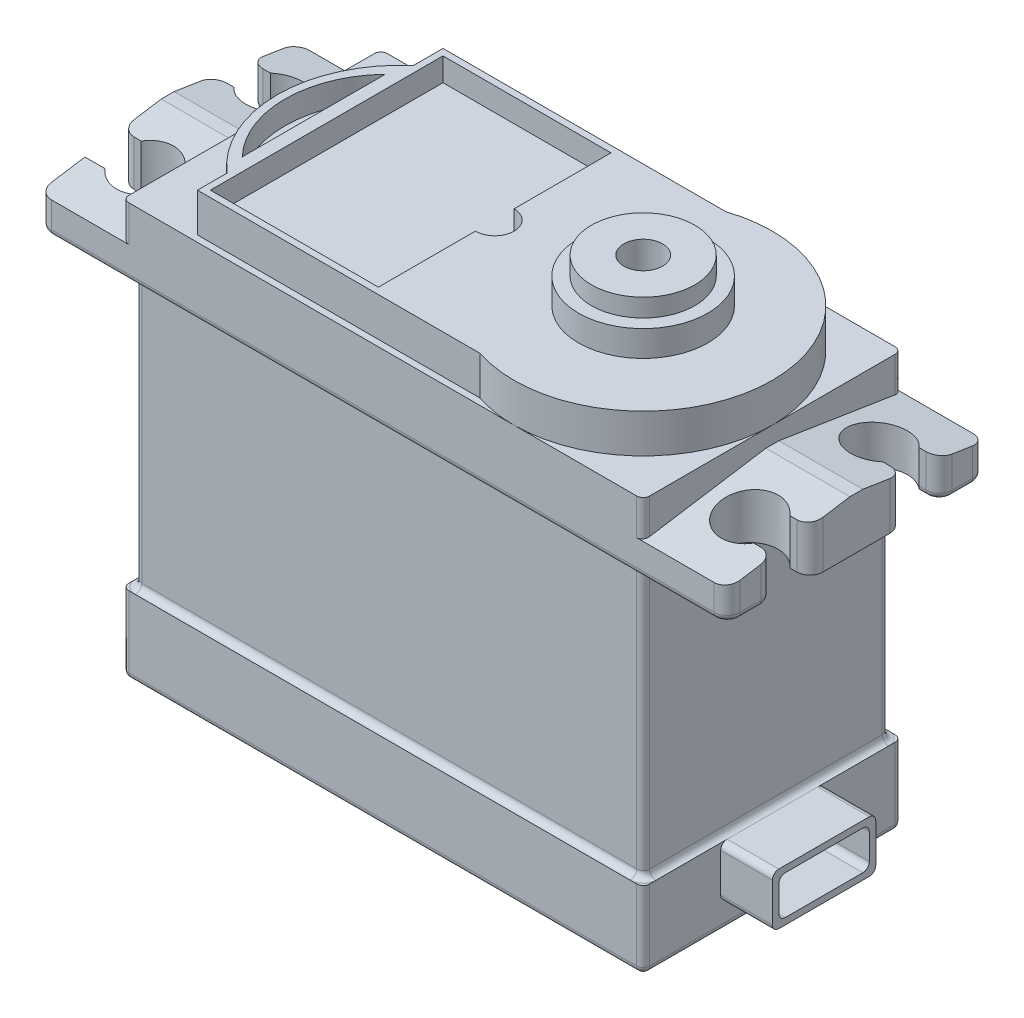
SolidWorks part; units mm, degrees
ref_plane "前基準面" through (0, 0, 0) normal (0, 0, 1) x (1, 0, 0)
ref_plane "上基準面" through (0, 0, 0) normal (0, 1, 0) x (1, 0, 0)
ref_plane "右基準面" through (0, 0, 0) normal (1, 0, 0) x (0, 0, -1)
sketch "草圖2" plane through (0, 0, 0) normal (0, 0, 1) x (1, 0, 0)
  line L1 (-17.6643, 8.7825) -> (22.6357, 8.7825)
  line L2 (-17.6643, 8.7825) -> (-17.6643, -23.2175)
  line L3 (-17.6643, -23.2175) -> (22.6357, -23.2175)
  line L4 (22.6357, 8.7825) -> (22.6357, -23.2175)
  dimension "D1" = 40.3
  dimension "D2" = 32
extrude "填料-伸長1" add sketch "草圖2" along normal blind 20 contours L2 L1 L4 L3
sketch "草圖3" plane through (22.6357, 0, 0) normal (1, 0, 0) x (0, 0, -1)
  line L2 (-20, 8.7825) -> (-20, -23.2175) construction
  line L3 (-20, 7.4825) -> (0, 7.4825)
  line L4 (-20, 7.4825) -> (-20, 3.4825)
  line L5 (-20, 3.4825) -> (0, 3.4825)
  line L6 (0, 7.4825) -> (0, 3.4825)
  line L7 (0, 8.7825) -> (0, -23.2175) construction
  line L9 (-20, -23.2175) -> (0, -23.2175) construction
  point P14 (0, 0)
  dimension "D1" = 26.7
  dimension "D2" = 4
extrude "填料-伸長2" add sketch "草圖3" along normal blind 6.5
sketch "草圖13" plane through (29.1357, 0, 0) normal (1, 0, 0) x (0, 0, -1)
  line L0 (-10, 7.4825) -> (-10, 3.4825) construction
  line L1 (0, 7.4825) -> (-20, 7.4825) construction
  line L2 (-20, 3.4825) -> (0, 3.4825) construction
  line L3 (-10.5, 7.4825) -> (-20, 5.9825)
  line L4 (-9.5, 3.4825) -> (-10.5, 3.4825)
  line L5 (-9.5, 3.4825) -> (-9.5, 7.4825)
  line L6 (-9.5, 7.4825) -> (-10.5, 7.4825)
  line L7 (-10.5, 3.4825) -> (-10.5, 7.4825)
  line L8 (-20, 7.4825) -> (-20, 3.4825) construction
  line L9 (-9.5, 7.4825) -> (0, 5.9825)
  line L10 (0, 3.4825) -> (0, 7.4825) construction
  point P10 (-10, 7.4825)
  line M5 (-20, 7.4825) -> (-20, 3.4825)
  line M7 (0, 3.4825) -> (0, 7.4825)
  line M8 (0, 7.4825) -> (-20, 7.4825)
  dimension "D1" = 1
  dimension "D2" = 2.5
  dimension "D3" = 2.5
extrude "除料-伸長4" cut sketch "草圖13" against normal up to surface (6.5 mm away) contours L3 M8 M5 | L9 M8 M7 region at (29.1357, 6.9825, 3.1667) region at (29.1357, 6.9825, 16.8333) up to face at (22.6357, 8.1325, 10)
sketch "草圖4" plane through (-17.6643, 0, 0) normal (-1, 0, 0) x (0, 0, 1)
  line L0 (10, -23.2175) -> (10, 3.3825) construction
  line L1 (20, -23.2175) -> (0, -23.2175) construction
  line L2 (0, 8.7825) -> (0, -23.2175) construction
  line L3 (0, 7.4825) -> (20, 7.4825)
  line L4 (0, 7.4825) -> (0, 3.4825)
  line L5 (0, 3.4825) -> (20, 3.4825)
  line L6 (20, 7.4825) -> (20, 3.4825)
  dimension "D1" = 26.6
  dimension "D2" = 4
extrude "填料-伸長3" add sketch "草圖4" along normal blind 6.5
sketch "草圖14" plane through (-24.1643, 0, 0) normal (-1, 0, 0) x (0, 0, 1)
  line L0 (10, 7.4825) -> (10, 3.4825) construction
  line L1 (20, 7.4825) -> (0, 7.4825) construction
  line L2 (0, 3.4825) -> (20, 3.4825) construction
  line L3 (9.5, 7.4825) -> (0, 5.9825)
  line L4 (9.5, 7.4825) -> (10.5, 7.4825)
  line L5 (9.5, 7.4825) -> (9.5, 3.4825)
  line L6 (9.5, 3.4825) -> (10.5, 3.4825)
  line L7 (10.5, 7.4825) -> (10.5, 3.4825)
  line L8 (0, 7.4825) -> (0, 3.4825) construction
  line L9 (10.5, 7.4825) -> (20, 5.9825)
  line L10 (20, 3.4825) -> (20, 7.4825) construction
  point P10 (10, 3.4825)
  line M5 (0, 7.4825) -> (0, 3.4825)
  line M7 (20, 3.4825) -> (20, 7.4825)
  line M8 (20, 7.4825) -> (0, 7.4825)
  dimension "D1" = 1
  dimension "D2" = 2.5
  dimension "D3" = 2.5
extrude "除料-伸長5" cut sketch "草圖14" against normal up to surface (6.5 mm away) contours L3 M8 M5 | L9 M8 M7 region at (-24.1643, 6.9825, 16.8333) region at (-24.1643, 6.9825, 3.1667) up to face at (-17.6643, 8.1325, 10)
sketch "草圖16" plane through (0, 0, 0) normal (0, 1, 0) x (1, 0, 0)
  line L0 (2.4857, 0) -> (2.4857, -20) construction
  line L1 (-24.1643, -20) -> (29.1357, -20)
  line L2 (-24.1643, -20) -> (-24.1643, 0)
  line L3 (-24.1643, 0) -> (29.1357, 0)
  line L4 (29.1357, -20) -> (29.1357, 0)
  line L5 (-17.6643, 0) -> (-24.1643, 0)
  line L6 (-20.9143, 0) -> (-20.9143, -20) construction
  line L7 (-24.1643, -10) -> (2.4857, -10) construction
  line L8 (-22.6114, -3.6) -> (-24.1643, -3.6)
  line L10 (-22.6114, -6.4) -> (-24.1643, -6.4)
  line L11 (-24.1643, -3.6) -> (-24.1643, -6.4)
  line L12 (-22.6114, -16.4) -> (-24.1643, -16.4)
  line L13 (-22.6114, -13.6) -> (-24.1643, -13.6)
  line L14 (27.5828, -16.4) -> (29.1357, -16.4)
  line L15 (27.5828, -13.6) -> (29.1357, -13.6)
  line L16 (27.5828, -3.6) -> (29.1357, -3.6)
  line L17 (27.5828, -6.4) -> (29.1357, -6.4)
  arc A0 (-22.6114, -6.4) -> (-22.6114, -3.6) centre (-20.9143, -5) ccw
  arc A1 (-22.6114, -13.6) -> (-22.6114, -16.4) centre (-20.9143, -15) cw
  arc A2 (27.5828, -13.6) -> (27.5828, -16.4) centre (25.8857, -15) ccw
  arc A3 (27.5828, -6.4) -> (27.5828, -3.6) centre (25.8857, -5) cw
  point P14 (-20.9143, -10)
  dimension "D1" = 4.4
  dimension "D2" = 5
  dimension "D3" = 3.6
  dimension "D4" = 3.1
extrude "除料-伸長6" cut sketch "草圖16" against normal blind 1.5 and the other way through all contours L10 A0 L8 L2 | A1 L13 L2 L12 | L15 A2 L14 L4 | A3 L17 L4 L16 region at (-21.3944, 0, 15) region at (26.3658, 0, 15) region at (-21.3944, 0, 5) region at (26.3658, 0, 5)
sketch "草圖7" plane through (22.6357, 0, 0) normal (1, 0, 0) x (0, 0, -1)
  line L1 (-20, -23.2175) -> (0, -23.2175) construction
  line L4 (-14, -17.2175) -> (-6, -17.2175)
  line L5 (-14, -17.2175) -> (-14, -21.2175)
  line L6 (-14, -21.2175) -> (-6, -21.2175)
  line L7 (-6, -17.2175) -> (-6, -21.2175)
  line L8 (-14, -17.2175) -> (-6, -21.2175) construction
  line L9 (-14, -21.2175) -> (-6, -17.2175) construction
  line L10 (-13.5, -17.7175) -> (-6.5, -17.7175)
  line L11 (-13.5, -17.7175) -> (-13.5, -20.7175)
  line L12 (-13.5, -20.7175) -> (-6.5, -20.7175)
  line L13 (-6.5, -17.7175) -> (-6.5, -20.7175)
  line L14 (-13.5, -17.7175) -> (-6.5, -20.7175) construction
  line L15 (-13.5, -20.7175) -> (-6.5, -17.7175) construction
  point P6 (-10, -19.2175)
  point P11 (-10, -19.2175)
  point P16 (0, 0)
  dimension "D1" = 2
  dimension "D2" = 8
  dimension "D3" = 4
  dimension "D4" = 0.5
  dimension "D5" = 0.5
extrude "填料-伸長4" add sketch "草圖7" along normal blind 4
sketch "草圖8" plane through (0, 8.7825, 0) normal (0, 1, 0) x (1, 0, 0)
  line L0 (-12.3544, -17.2064) -> (-12.3544, -19.5)
  line L1 (9.5132, -0.5) -> (-12.3544, -0.5)
  line L3 (-17.6643, -20) -> (-17.6643, 0) construction
  line L4 (9.5132, -19.5) -> (-12.3544, -19.5)
  line L5 (-12.3544, -0.5) -> (-12.3544, -2.7936)
  arc A0 (9.5132, -19.5) -> (9.5132, -0.5) centre (12.6357, -10) ccw
  arc A1 (-12.3544, -2.7936) -> (-12.3544, -17.2064) centre (-6.1643, -10) ccw
  point P0 (-15.6643, -10)
  point P10 (22.6357, -10)
  dimension "D2" = 9.5
  dimension "D1" = 10
  dimension "D3" = 2
extrude "填料-伸長5" add sketch "草圖8" along normal blind 3
sketch "草圖9" plane through (0, 11.7825, 0) normal (0, 1, 0) x (1, 0, 0)
  line L0 (22.6357, -10) -> (-15.6643, -10) construction
  arc A0 (9.5132, -19.5) -> (9.5132, -0.5) centre (12.6357, -10) ccw construction
  arc A1 (-12.3544, -2.7936) -> (-12.3544, -17.2064) centre (-6.1643, -10) ccw construction
  circle A2 centre (12.6357, -10) radius 5
  dimension "D1" = 10
extrude "填料-伸長6" add sketch "草圖9" along normal blind 2
sketch "草圖10" plane through (0, 13.7825, 0) normal (0, 1, 0) x (1, 0, 0)
  circle A0 centre (12.6357, -10) radius 4
  circle A1 centre (12.6357, -10) radius 5 construction
  dimension "D1" = 1
extrude "填料-伸長7" add sketch "草圖10" along normal blind 1.4
sketch "草圖11" plane through (0, 15.1825, 0) normal (0, 1, 0) x (1, 0, 0)
  circle A0 centre (12.6357, -10) radius 1.5
  dimension "D1" = 3
extrude "除料-伸長3" cut sketch "草圖11" against normal blind 6.4
sketch "草圖17" plane through (22.6357, 0, 0) normal (1, 0, 0) x (0, 0, -1)
  line L0 (0, 3.4825) -> (0, -23.2175) construction
  line L1 (-20, 3.4825) -> (0, 3.4825)
  line L2 (-20, 3.4825) -> (-20, -17.2175)
  line L3 (-20, -17.2175) -> (0, -17.2175)
  line L4 (0, 3.4825) -> (0, -17.2175)
extrude "除料-伸長7" cut sketch "草圖17" against normal blind 0.5
sketch "草圖18" plane through (0, 0, 20) normal (0, 0, 1) x (1, 0, 0)
  line L1 (-17.6643, 3.4825) -> (22.1357, 3.4825)
  line L2 (-17.6643, 3.4825) -> (-17.6643, -17.2175)
  line L3 (-17.6643, -17.2175) -> (22.1357, -17.2175)
  line L4 (22.1357, 3.4825) -> (22.1357, -17.2175)
extrude "除料-伸長8" cut sketch "草圖18" against normal blind 0.5
sketch "草圖19" plane through (-17.6643, 0, 0) normal (-1, 0, 0) x (0, 0, 1)
  line L1 (0, 3.4825) -> (19.5, 3.4825)
  line L2 (0, 3.4825) -> (0, -17.2175)
  line L3 (0, -17.2175) -> (19.5, -17.2175)
  line L4 (19.5, 3.4825) -> (19.5, -17.2175)
extrude "除料-伸長9" cut sketch "草圖19" against normal blind 0.5
sketch "草圖20" plane through (0, 0, 0) normal (0, 0, -1) x (-1, 0, 0)
  line L1 (-22.1357, 3.4825) -> (17.1643, 3.4825)
  line L2 (-22.1357, 3.4825) -> (-22.1357, -17.2175)
  line L3 (-22.1357, -17.2175) -> (17.1643, -17.2175)
  line L4 (17.1643, 3.4825) -> (17.1643, -17.2175)
extrude "除料-伸長10" cut sketch "草圖20" against normal blind 0.5
fillet "圓角5" radius 1 11 edges at (29.1357, 4.7325, 0) (29.1357, 5.0168, 3.6) (29.1357, 5.2378, 6.4) (29.1357, 5.2378, 13.6) (29.1357, 5.0168, 16.4) (29.1357, 4.7325, 20) (-24.1643, 5.2378, 13.6) (-24.1643, 5.2378, 6.4) (-24.1643, 5.0168, 3.6) (-24.1643, 4.7325, 0) (-24.1643, 4.7325, 20) tangent propagation no
fillet "圓角6" radius 0.5 12 edges at (22.6357, -20.2175, 0) (22.6357, -20.2175, 20) (-17.6643, -20.2175, 20) (-17.6643, -20.2175, 0) (-17.1643, -6.8675, 0.5) (-17.1643, -6.8675, 19.5) (22.1357, -6.8675, 19.5) (22.1357, -6.8675, 0.5) (22.6357, 7.3825, 0) (22.6357, 7.3825, 20) (-17.6643, 7.3825, 0) (-17.6643, 7.3825, 20)
fillet "圓角7" radius 0.5 16 edges at (-17.5179, -23.2175, 19.8536) (-17.6643, -23.2175, 10) (-17.5179, -23.2175, 0.1464) (2.4857, -23.2175, 0) (22.4892, -23.2175, 0.1464) (22.6357, -23.2175, 10) (22.4892, -23.2175, 19.8536) (-17.0179, -17.2175, 19.3536) (-17.1643, -17.2175, 10) (-17.0179, -17.2175, 0.6464) (2.4857, -17.2175, 0.5) (21.9892, -17.2175, 0.6464) (22.1357, -17.2175, 10) (21.9892, -17.2175, 19.3536) (2.4857, -23.2175, 20) (2.4857, -17.2175, 19.5)
fillet "圓角8" radius 0.5 16 edges at (27.8592, 3.4825, 3.6) (28.8428, 3.4825, 3.3071) (29.1357, 3.4825, 1.8) (28.8428, 3.4825, 0.2929) (-22.8878, 3.4825, 3.6) (-23.8714, 3.4825, 3.3071) (-24.1643, 3.4825, 1.8) (-23.8714, 3.4825, 0.2929) (27.8592, 3.4825, 16.4) (28.8428, 3.4825, 16.6929) (29.1357, 3.4825, 18.2) (28.8428, 3.4825, 19.7071) (-24.1643, 3.4825, 17.7) (-23.8714, 3.4825, 19.7071) (2.4857, 3.4825, 0) (2.4857, 3.4825, 20)
fillet "圓角9" radius 0.5 8 edges at (24.6357, -20.7175, 6.5) (24.6357, -20.7175, 13.5) (24.6357, -17.7175, 6.5) (24.6357, -17.2175, 6) (24.6357, -21.2175, 6) (24.6357, -21.2175, 14) (24.6357, -17.7175, 13.5) (24.6357, -17.2175, 14)
sketch "草圖22" plane through (0, 11.7825, 0) normal (0, 1, 0) x (1, 0, 0)
  line L1 (-12.3544, -0.5) -> (-12.3544, -2.7936) construction
  line L2 (1.1456, -1) -> (-11.8544, -1)
  line L12 (-12.8544, -4.4633) -> (-12.8544, -15.5367)
  line L13 (1.1456, -1) -> (1.1456, -8.5)
  line L14 (1.1456, -19) -> (-11.8544, -19)
  line L15 (-11.8544, -1) -> (-11.8544, -19)
  line L16 (9.5132, -0.5) -> (-12.3544, -0.5) construction
  line L17 (-12.3544, -19.5) -> (9.5132, -19.5) construction
  line L18 (1.1456, -11.5) -> (1.1456, -19)
  arc A1 (-12.8544, -4.4633) -> (-12.8544, -15.5367) centre (-7.0799, -10) ccw
  arc A5 (1.1456, -11.5) -> (1.1456, -8.5) centre (1.1456, -10) ccw
  dimension "D2" = 0.5
  dimension "D5" = 0.5
  dimension "D3" = 0.5
  dimension "D4" = 13
  dimension "D6" = 8
  dimension "D1" = 0.5
extrude "除料-伸長12" cut sketch "草圖22" against normal blind 1.8
